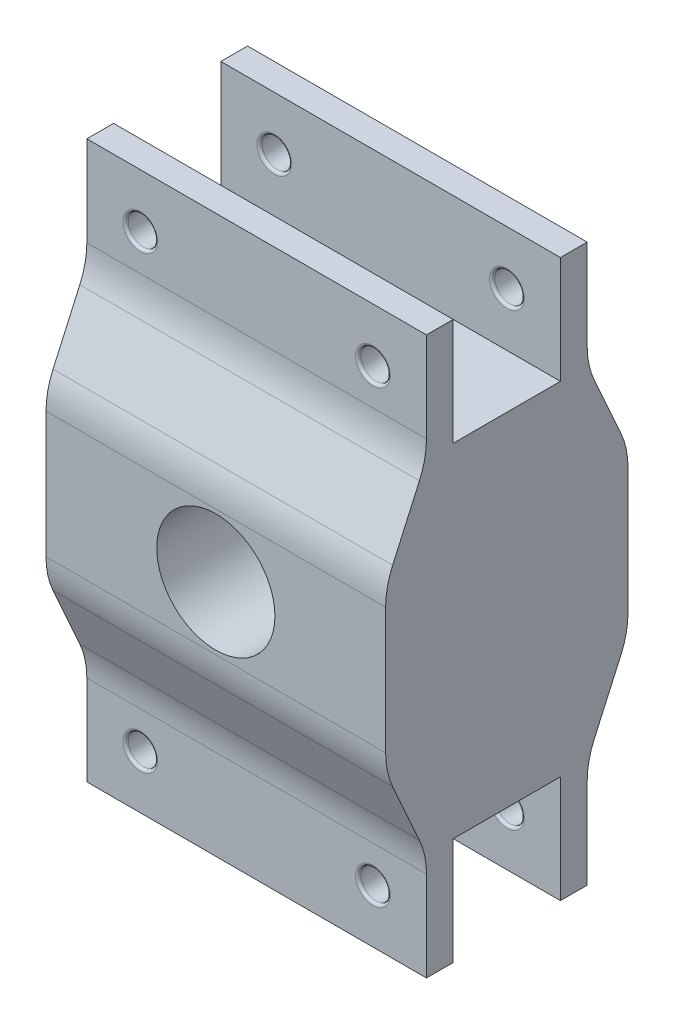
SolidWorks part; units mm, degrees
ref_plane "Front Plane" through (0, 0, 0) normal (0, 0, 1) x (1, 0, 0)
ref_plane "Top Plane" through (0, 0, 0) normal (0, 1, 0) x (1, 0, 0)
ref_plane "Right Plane" through (0, 0, 0) normal (1, 0, 0) x (0, 0, -1)
sketch "Sketch1" plane through (0, 0, 0) normal (1, 0, 0) x (0, 0, -1)
  line L0 (-15.025, 32.02) -> (-22.6575, 15)
  line L1 (0, 0) -> (50000, 0) construction
  line L3 (-10.025, 52.07) -> (-10.025, 32.02)
  line L6 (-10.025, 32.02) -> (10.025, 32.02)
  line L7 (-10.025, 52.07) -> (-15.025, 52.07)
  line L8 (-15.025, 52.07) -> (-15.025, 32.02)
  line L20 (-22.6575, 15) -> (-22.6575, -15)
  line L28 (0, 0) -> (0, 50000) construction
  line L29 (22.6575, 15) -> (22.6575, -15)
  line L30 (15.025, 52.07) -> (15.025, 32.02)
  line L31 (10.025, 52.07) -> (15.025, 52.07)
  line L32 (10.025, 52.07) -> (10.025, 32.02)
  line L33 (15.025, 32.02) -> (22.6575, 15)
  line L34 (15.025, -32.02) -> (22.6575, -15)
  line L35 (10.025, -52.07) -> (10.025, -32.02)
  line L36 (10.025, -52.07) -> (15.025, -52.07)
  line L37 (15.025, -52.07) -> (15.025, -32.02)
  line L38 (-15.025, -52.07) -> (-15.025, -32.02)
  line L39 (-10.025, -52.07) -> (-15.025, -52.07)
  line L40 (-10.025, -32.02) -> (10.025, -32.02)
  line L41 (-10.025, -52.07) -> (-10.025, -32.02)
  line L42 (-15.025, -32.02) -> (-22.6575, -15)
  point P17 (0, 32.02)
  point P22 (22.6575, 0)
  point P23 (-22.6575, 0)
  point P27 (0, -32.02)
  dimension "D5" = 20.05
  dimension "D6" = 52.07
  dimension "D1" = 10.025
  dimension "D2" = 15
  dimension "D3" = 5
extrude "Boss-Extrude1" add sketch "Sketch1" along normal mid plane 63.5
sketch "Sketch2" plane through (0, 0, 15.025) normal (0, 0, 1) x (1, 0, 0)
  line L1 (31.75, 52.07) -> (-31.75, 52.07) construction
  line L2 (-31.75, 52.07) -> (-31.75, 32.02) construction
  line L3 (0, 0) -> (0, 19.2106) construction
  circle A5 centre (-21.75, 42.07) radius 2.75
  circle A6 centre (21.75, 42.07) radius 2.75
  dimension "D2" = 10
  dimension "D1" = 5.5
  dimension "D3" = 10
extrude "Cut-Extrude1" cut sketch "Sketch2" against normal through all
mirror "Mirror1" about plane through (0, 0, 0) normal (0, 1, 0) of "Cut-Extrude1"
sketch "Sketch3" plane through (0, 0, 22.6575) normal (0, 0, 1) x (1, 0, 0)
  circle A0 centre (0, 0) radius 11.049
  dimension "D1" = 22.098
extrude "Cut-Extrude2" cut sketch "Sketch3" against normal through all
fillet "Fillet1" radius 0.5 15 edges at (-21.75, 44.82, -10.025) (24.5, 42.07, -15.025) (21.75, 44.82, -10.025) (21.75, 39.32, 10.025) (19, 42.07, 15.025) (-21.75, 39.32, 10.025) (-19, 42.07, 15.025) (21.75, -39.32, -10.025) (24.5, -42.07, -15.025) (-21.75, -39.32, -10.025) (-19, -42.07, -15.025) (21.75, -44.82, 10.025) (19, -42.07, 15.025) (-21.75, -44.82, 10.025) (-19, -42.07, 15.025)
fillet "Fillet2" radius 15 8 edges at (0, 32.02, -15.025) (0, 15, -22.6575) (0, -15, -22.6575) (0, -32.02, -15.025) (0, -32.02, 15.025) (0, -15, 22.6575) (0, 15, 22.6575) (0, 32.02, 15.025)
